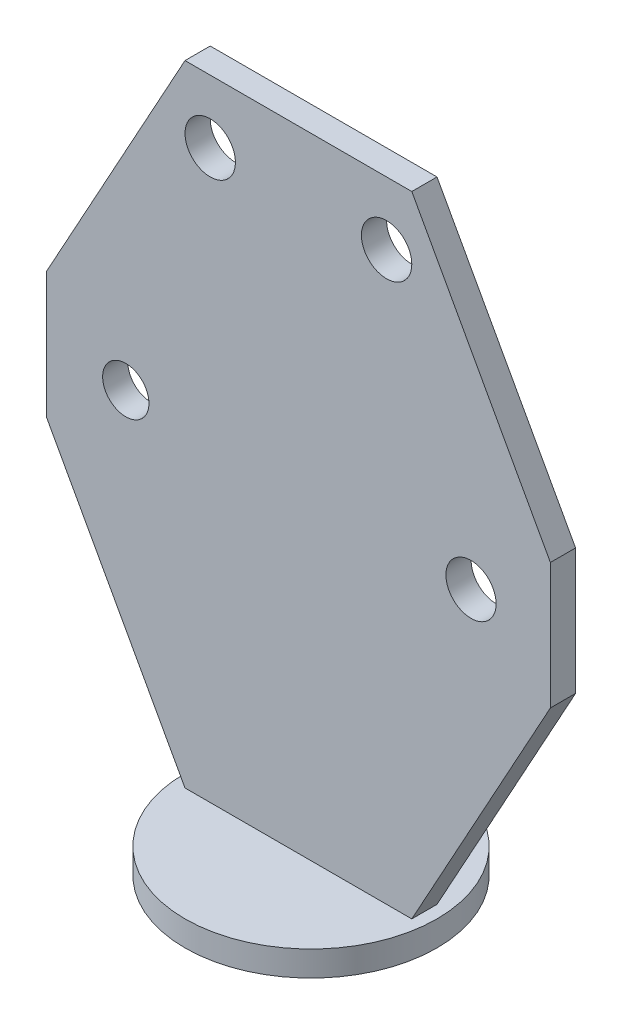
SolidWorks part; units mm, degrees
material "可锻铸铁"
ref_plane "前视基准面" through (0, 0, 0) normal (0, 0, 1) x (1, 0, 0)
ref_plane "上视基准面" through (0, 0, 0) normal (0, 1, 0) x (1, 0, 0)
ref_plane "右视基准面" through (0, 0, 0) normal (1, 0, 0) x (0, 0, -1)
sketch "草图1" plane through (0, 0, 0) normal (0, 1, 0) x (1, 0, 0)
  circle A0 centre (0, 0) radius 10
  dimension "D1" = 20
extrude "凸台-拉伸1" add sketch "草图1" along normal blind 2
sketch "草图3" plane through (0, 0, 0) normal (0, 0, 1) x (1, 0, 0)
  line L1 (9, 2) -> (-9, 2)
  line L2 (20, 22) -> (20, 32)
  line L3 (9, 52) -> (-9, 52)
  line L4 (-20, 22) -> (-20, 32)
  line L5 (-9, 52) -> (-20, 32)
  line L6 (9, 52) -> (20, 32)
  line L7 (-20, 22) -> (-9, 2)
  line L8 (20, 22) -> (9, 2)
  circle A0 centre (-7, 47) radius 2
  circle A1 centre (7, 47) radius 2
  circle A2 centre (13.7, 27) radius 1.9924
  circle A3 centre (-13.7, 27) radius 1.8367
  point P15 (0, 2)
  dimension "D12" = 4
  dimension "D13" = 4
  dimension "D3" = 0
  dimension "D4" = 10
  dimension "D5" = 10
  dimension "D7" = 9
  dimension "D10" = 9
  dimension "D11" = 18
  dimension "D14" = 5
  dimension "D15" = 5
  dimension "D16" = 2
  dimension "D17" = 2
  dimension "D18" = 6.3
  dimension "D19" = 6.3
extrude "凸台-拉伸2" add sketch "草图3" along normal blind 1 and the other way blind 1
